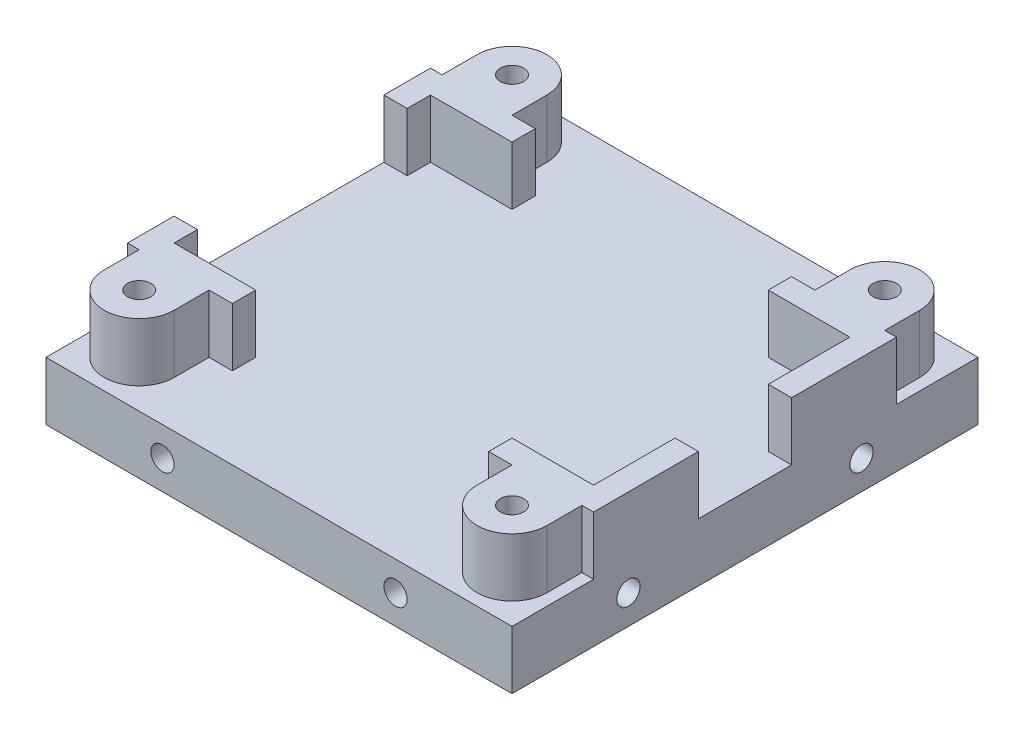
SolidWorks part; units mm, degrees
ref_plane "Front Plane" through (0, 0, 0) normal (0, 0, 1) x (1, 0, 0)
ref_plane "Top Plane" through (0, 0, 0) normal (0, 1, 0) x (1, 0, 0)
ref_plane "Right Plane" through (0, 0, 0) normal (1, 0, 0) x (0, 0, -1)
sketch "Sketch1" plane through (0, 0, 0) normal (0, 1, 0) x (1, 0, 0)
  line L1 (-20, -20) -> (20, -20)
  line L2 (-20, -20) -> (-20, 20)
  line L3 (-20, 20) -> (20, 20)
  line L4 (20, -20) -> (20, 20)
  line L5 (-20, -20) -> (20, 20) construction
  line L6 (-20, 20) -> (20, -20) construction
  point P0 (0, 0)
  dimension "D1" = 40
  dimension "D2" = 40
extrude "Boss-Extrude1" add sketch "Sketch1" along normal blind 5
sketch "Sketch3" plane through (0, 5, 0) normal (0, 1, 0) x (1, 0, 0)
  line L0 (13, 11) -> (18, 11)
  line L5 (-18, -11) -> (18, -11)
  line L6 (-18, -11) -> (-18, 11)
  line L7 (-18, 11) -> (18, 11)
  line L8 (18, -11) -> (18, 11)
  line L9 (-18, -11) -> (18, 11) construction
  line L10 (-18, 11) -> (18, -11) construction
  line L11 (-20, -9) -> (-16, -9)
  line L12 (-20, -9) -> (-20, 9)
  line L13 (-20, 9) -> (-16, 9)
  line L14 (-16, -9) -> (-16, 9)
  line L15 (-20, -9) -> (-16, 9) construction
  line L16 (-20, 9) -> (-16, -9) construction
  line L17 (18, 11) -> (13, 11)
  line L18 (18, 11) -> (18, 6)
  line L19 (18, 6) -> (13, 6)
  line L20 (13, 11) -> (13, 6)
  line L21 (20, 13) -> (20, 4)
  line L22 (20, 4) -> (11, 4)
  line L23 (11, 13) -> (11, 4)
  line L24 (20, 13) -> (11, 13)
  line L25 (-11, 13) -> (-11, 4)
  line L26 (-11, 4) -> (-20, 4)
  line L27 (-20, 13) -> (-20, 4)
  line L28 (-11, 13) -> (-20, 13)
  line L29 (-11, -4) -> (-11, -13)
  line L30 (-11, -13) -> (-20, -13)
  line L31 (-20, -4) -> (-20, -13)
  line L32 (-11, -4) -> (-20, -4)
  line L33 (20, -4) -> (20, -13)
  line L34 (20, -13) -> (11, -13)
  line L35 (11, -4) -> (11, -13)
  line L36 (20, -4) -> (11, -4)
  line L37 (13, 16) -> (13, 13)
  line L38 (-19, 16) -> (-13, 16)
  line L39 (-19, 16) -> (-19, 13)
  line L40 (-19, 13) -> (-13, 13)
  line L41 (-13, 16) -> (-13, 13)
  line L42 (13, 16) -> (19, 16)
  line L43 (19, 16) -> (19, 13)
  line L44 (13, 13) -> (19, 13)
  line L45 (13, -13) -> (13, -16)
  line L46 (13, -13) -> (19, -13)
  line L47 (19, -13) -> (19, -16)
  line L48 (13, -16) -> (19, -16)
  line L49 (-19, -13) -> (-19, -16)
  line L50 (-19, -13) -> (-13, -13)
  line L51 (-13, -13) -> (-13, -16)
  line L52 (-19, -16) -> (-13, -16)
  circle A0 centre (16, 16) radius 1
  circle A1 centre (-16, 16) radius 1
  circle A2 centre (-16, -16) radius 1
  circle A3 centre (16, -16) radius 1
  circle A4 centre (-16, 16) radius 3
  circle A5 centre (16, 16) radius 3
  circle A6 centre (-16, -16) radius 3
  circle A7 centre (16, -16) radius 3
  point P0 (0, 0)
  point P14 (0, 0)
  point P19 (-18, 0)
  line M24 (20, -20) -> (20, 20)
  line M26 (-20, 20) -> (-20, -20)
  dimension "D3" = 22
  dimension "D1" = 32
  dimension "D2" = 32
  dimension "D4" = 36
  dimension "D5" = 18
  dimension "D6" = 5
  dimension "D7" = 5
  dimension "D10" = 6
  dimension "D8" = 2
  dimension "D9" = 2
  dimension "D11" = 2
  dimension "D12" = 2
extrude "Boss-Extrude3" add sketch "Sketch3" along normal blind 5 contours L38 A4 A1 | A4 L38 A1 | L25 L28 L40 L13 L6 L7 M26 | L24 L44 L23 L7 L0 L8 L22 M24 | A5 L37 L44 | A5 L24 L43 | A5 L42 A0 | L42 A5 A0 | L36 L8 L5 L35 L34 L46 M24 | L48 A7 A3 | L52 A6 A2 | L52 A2 | L30 L29 L5 L6 L11 L50 M26 | L41 L40 L39 L38 | L47 L48 L45 L46 | L51 L52 L49 L50 | A3 region at (12, 5, -11.1273) region at (-16.1364, 5, -11.6364) region at (13.6701, 5, -13.6701) region at (19, 5, 4.1273) region at (18.3299, 5, -13.6701) region at (16, 5, -14.6207) region at (16, 5, -17.3793) region at (-16, 5, -14.6207) region at (-16, 5, -17.3793) region at (-16.1364, 5, 11.6364) region at (16, 5, 17.3793) region at (-16, 5, 17.3793) region at (-16, 5, 15.5756)
extrude "Cut-Extrude1" cut sketch "Sketch3<4>" along normal blind 5 contours A3 | A2 | A1
sketch "Sketch3<4>" plane through (0, 5, 0) normal (0, 1, 0) x (1, 0, 0) same geometry as "Sketch3"
sketch "Sketch4" plane through (-20, 0, 0) normal (-1, 0, 0) x (0, 0, 1)
  circle A0 centre (-10, 2.5) radius 1
  circle A1 centre (10, 2.5) radius 1
extrude "Cut-Extrude2" cut sketch "Sketch4" against normal blind 10
pattern_circular "CirPattern2" count 4 every 90 about axis through (0, 0, 0) along (0, -1, 0) of "Cut-Extrude2"
